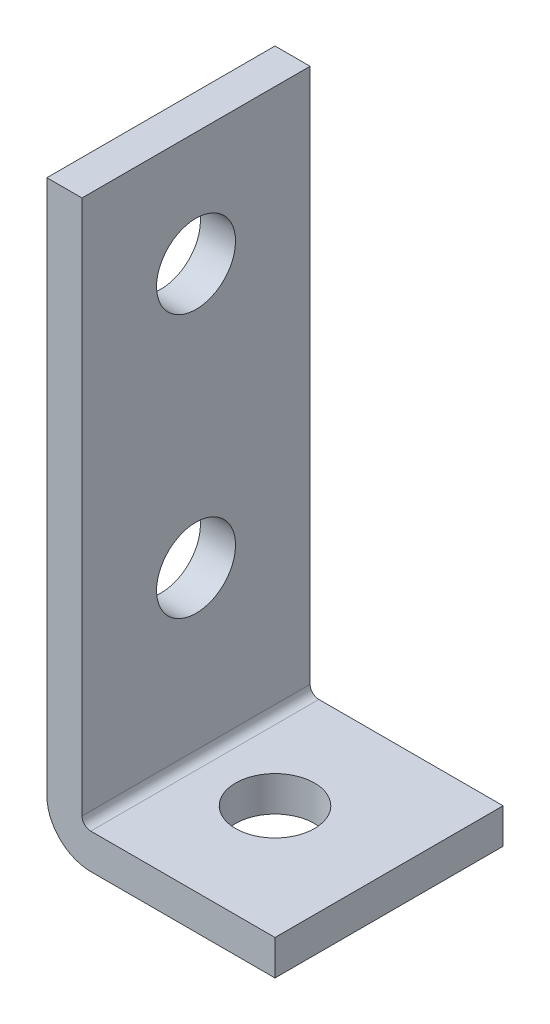
SolidWorks part; units mm, degrees
ref_plane "Front Plane" through (0, 0, 0) normal (0, 0, 1) x (1, 0, 0)
ref_plane "Top Plane" through (0, 0, 0) normal (0, 1, 0) x (1, 0, 0)
ref_plane "Right Plane" through (0, 0, 0) normal (1, 0, 0) x (0, 0, -1)
sketch "Sketch1" plane through (0, 0, 0) normal (0, 0, 1) x (1, 0, 0)
  line L0 (0, 104.775) -> (0, 7.9375)
  line L1 (7.9375, 0) -> (41.275, 0)
  arc A0 (0, 7.9375) -> (7.9375, 0) centre (7.9375, 7.9375) ccw
  dimension "D1" = 7.9375
  dimension "B" = 41.275
  dimension "A" = 104.775
extrude "Extrude-Thin1" add sketch "Sketch1" along normal mid plane 41.275 thin thin type one direction reverse wall 6.35
sketch "Sketch2" plane through (0, 6.35, 0) normal (0, 1, 0) x (1, 0, 0)
  line L0 (41.275, -20.6375) -> (41.275, 20.6375) construction
  circle A0 centre (20.6375, 0) radius 7.1438
  dimension "Hole Size" = 14.2875
  dimension "edge" = 20.6375
extrude "Cut-Extrude1" cut sketch "Sketch2" against normal through all
sketch "Sketch3" plane through (6.35, 0, 0) normal (1, 0, 0) x (0, 0, -1)
  line L0 (-20.6375, 104.775) -> (20.6375, 104.775) construction
  circle A0 centre (0, 84.1375) radius 7.1438
  circle A1 centre (0, 36.5125) radius 7.1438
  dimension "D2" = 14.2875
  dimension "D1" = 20.6375
  dimension "Hole Spacing" = 47.625
extrude "Cut-Extrude2" cut sketch "Sketch3" against normal through all
equation "\"D2@Sketch3\" = \"Hole Size@Sketch2\""
